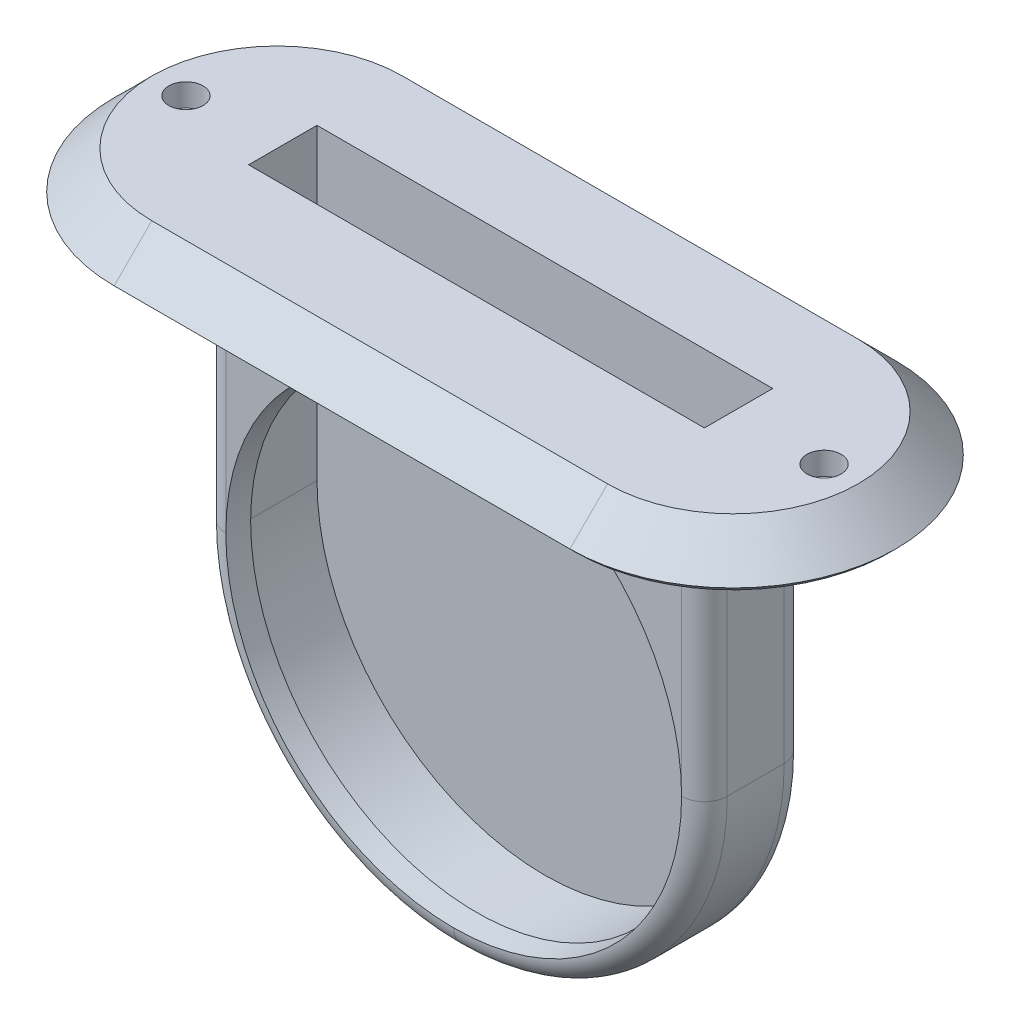
SolidWorks part; units mm, degrees
ref_plane "Plan de face" through (0, 0, 0) normal (0, 0, 1) x (1, 0, 0)
ref_plane "Plan de dessus" through (0, 0, 0) normal (0, 1, 0) x (1, 0, 0)
ref_plane "Plan de droite" through (0, 0, 0) normal (1, 0, 0) x (0, 0, -1)
sketch "Esquisse1" plane through (0, 0, 0) normal (0, 1, 0) x (1, 0, 0)
  line L0 (-20, 0) -> (20, 0) construction
  line L1 (-20, 14.8) -> (20, 14.8)
  line L2 (-20, -14.8) -> (20, -14.8)
  arc A0 (-20, 14.8) -> (-20, -14.8) centre (-20, 0) ccw
  arc A1 (20, -14.8) -> (20, 14.8) centre (20, 0) ccw
  point P3 (0, 0)
  dimension "D1" = 14.8
  dimension "D2" = 40
extrude "Boss.-Extru.1" add sketch "Esquisse1" along normal blind 3.8 draft 45
shell "Coque2" thickness 2 removed face at (0, 0, 0)
chamfer "Chanfrein1" distance 1 angle 45 4 edges at (-34.8, 0, 0) (0, 0, 14.8) (0, 0, -14.8) (34.8, 0, 0) first distance on face at (0, 0, 0)
sketch "Esquisse2" plane through (0, 3.8, 0) normal (0, 1, 0) x (1, 0, 0)
  line L0 (0, 11) -> (0, -11) construction
  line L1 (20, 11) -> (-20, 11) construction
  line L2 (-20, -11) -> (20, -11) construction
  circle A0 centre (-28, 0) radius 1.5
  circle A1 centre (28, 0) radius 1.5
  point P2 (0, 0)
  dimension "D1" = 3
  dimension "D2" = 8
extrude "Enlèv. mat.-Extru.1" cut sketch "Esquisse2" against normal up to next
sketch "Esquisse3" plane through (0, 1.8, 0) normal (0, -1, 0) x (1, 0, 0)
  line L0 (-22, -4.5) -> (22, 4.5) construction
  line L1 (-22, -4.5) -> (22, -4.5)
  line L2 (-22, -4.5) -> (-22, 4.5)
  line L7 (-22, 4.5) -> (22, 4.5)
  line L9 (22, -4.5) -> (22, 4.5)
  point P1 (0, 0)
  dimension "D1" = 44
  dimension "D2" = 9
extrude "Boss.-Extru.4" add sketch "Esquisse3" along normal blind 47
fillet "Congé1" radius 22 2 edges at (22, -45.2, 0) (-22, -45.2, 0)
fillet "Congé2" radius 2 8 edges at (22, -10.7, -4.5) (15.5563, -38.7563, -4.5) (-22, -10.7, -4.5) (-22, -10.7, 4.5) (-15.5563, -38.7563, 4.5) (22, -10.7, 4.5) (-15.5563, -38.7563, -4.5) (15.5563, -38.7563, 4.5)
sketch "Esquisse7" plane through (0, 0, 4.5) normal (0, 0, 1) x (1, 0, 0)
  circle A0 centre (0, -23.2) radius 20
  arc A2 (0, -43.2) -> (20, -23.2) centre (0, -23.2) ccw construction
extrude "Enlèv. mat.-Extru.4" cut sketch "Esquisse7" against normal blind 2 draft 5
sketch "Esquisse9" plane through (0, 0, 2.5) normal (0, 0, 1) x (1, 0, 0)
  line L0 (20, -23.2) -> (20, 1.8) construction
  line L1 (-20, 1.8) -> (-20, -23.2) construction
  line L2 (-20, -23.2) -> (-20, 3.8)
  line L3 (-20, 3.8) -> (20, 3.8)
  line L4 (20, 3.8) -> (20, -23.2)
  arc A0 (20, -23.2) -> (-20, -23.2) centre (0, -23.2) cw
  arc A1 (0, -43.2) -> (20, -23.2) centre (0, -23.2) ccw construction
extrude "Enlèv. mat.-Extru.5" cut sketch "Esquisse9" against normal blind 6
